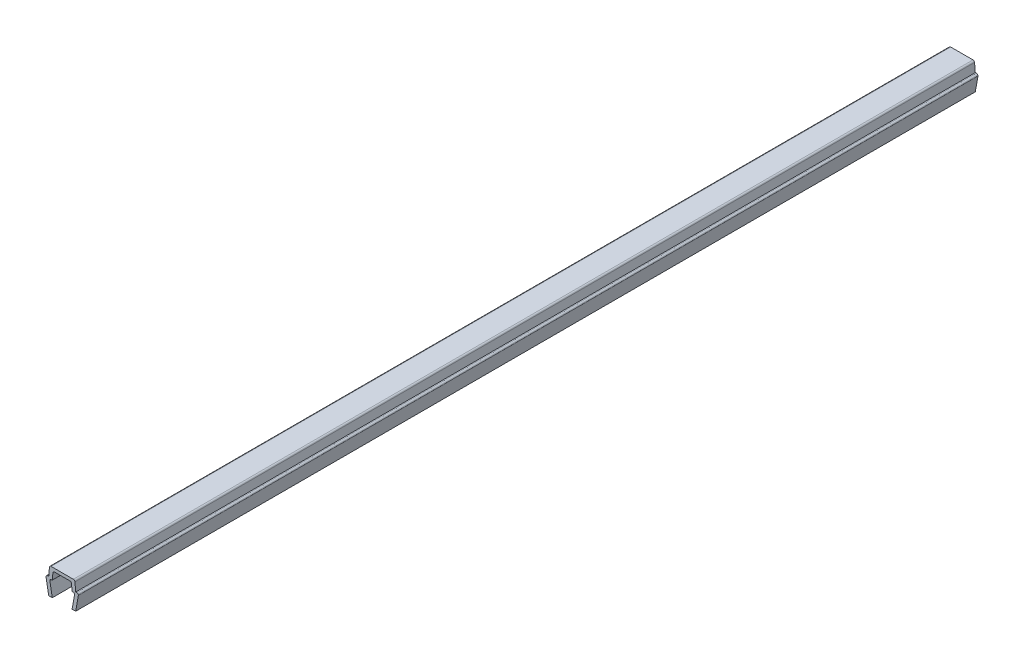
SolidWorks part; units mm, degrees
ref_plane "Front Plane" through (0, 0, 0) normal (0, 0, 1) x (1, 0, 0)
ref_plane "Top Plane" through (0, 0, 0) normal (0, 1, 0) x (1, 0, 0)
ref_plane "Right Plane" through (0, 0, 0) normal (1, 0, 0) x (0, 0, -1)
ref_plane "Plane1" through (0, 0, 0) normal (0, 0, 1) x (1, 0, 0)
sketch "Sketch1" plane through (0, 0, 0) normal (0, 0, 1) x (1, 0, 0)
  line L0 (-3.6, 3.35) -> (-3, 0)
  line L1 (-3, 0) -> (-2.2, 0)
  line L2 (-2.2, 0) -> (-2.7352, 2.9883)
  line L3 (-2.3907, 3.4) -> (-2.2, 3.4)
  line L4 (-2.2, 3.4) -> (-2.0705, 4.8805)
  line L5 (-1.7218, 5.2) -> (1.7218, 5.2)
  line L6 (2.0705, 4.8805) -> (2.2, 3.4)
  line L7 (2.2, 3.4) -> (2.3907, 3.4)
  line L8 (2.7352, 2.9883) -> (2.2, 0)
  line L9 (2.2, 0) -> (3, 0)
  line L10 (3, 0) -> (3.6, 3.35)
  line L11 (3.25, 3.7) -> (3, 3.7)
  line L12 (3, 3.7) -> (2.8355, 5.5805)
  line L13 (2.4868, 5.9) -> (-2.4868, 5.9)
  line L14 (-2.8355, 5.5805) -> (-3, 3.7)
  line L15 (-3, 3.7) -> (-3.25, 3.7)
  arc A0 (-2.7352, 2.9883) -> (-2.3907, 3.4) centre (-2.3907, 3.05) cw
  arc A1 (-2.0705, 4.8805) -> (-1.7218, 5.2) centre (-1.7218, 4.85) cw
  arc A2 (1.7218, 5.2) -> (2.0705, 4.8805) centre (1.7218, 4.85) cw
  arc A3 (2.3907, 3.4) -> (2.7352, 2.9883) centre (2.3907, 3.05) cw
  arc A4 (3.6, 3.35) -> (3.25, 3.7) centre (3.25, 3.35) ccw
  arc A5 (2.8355, 5.5805) -> (2.4868, 5.9) centre (2.4868, 5.55) ccw
  arc A6 (-2.4868, 5.9) -> (-2.8355, 5.5805) centre (-2.4868, 5.55) ccw
  arc A7 (-3.25, 3.7) -> (-3.6, 3.35) centre (-3.25, 3.35) ccw
extrude "Boss-Extrude1" add sketch "Sketch1" against normal mid plane 200
